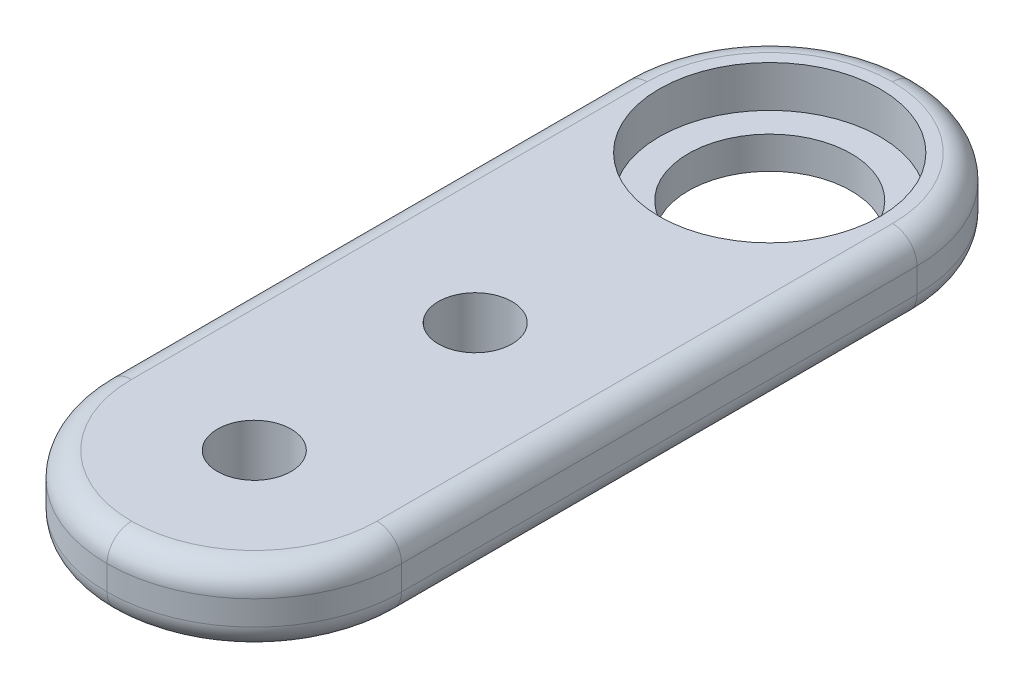
SolidWorks part; units mm, degrees
material "6061 Alloy"
ref_plane "Front Plane" through (0, 0, 0) normal (0, 0, 1) x (1, 0, 0)
ref_plane "Top Plane" through (0, 0, 0) normal (0, 1, 0) x (1, 0, 0)
ref_plane "Right Plane" through (0, 0, 0) normal (1, 0, 0) x (0, 0, -1)
sketch "Sketch1" plane through (0, 0, 0) normal (0, 1, 0) x (1, 0, 0)
  line L0 (0, 34.925) -> (0, -34.925) construction
  line L1 (-12.7, -34.925) -> (12.7, -34.925)
  line L2 (-12.7, -34.925) -> (-12.7, 34.925)
  line L3 (-12.7, 34.925) -> (12.7, 34.925)
  line L4 (12.7, -34.925) -> (12.7, 34.925)
  line L5 (-12.7, -34.925) -> (12.7, 34.925) construction
  line L6 (-12.7, 34.925) -> (12.7, -34.925) construction
  circle A1 centre (0, -3.175) radius 3.175
  circle A2 centre (0, -22.225) radius 3.175
  point P0 (0, 0)
  point P8 (0, 22.225)
  dimension "D3" = 25.4
  dimension "D2" = 12.7
  dimension "D6" = 6.35
  dimension "D1" = 25.4
  dimension "D4" = 19.05
  dimension "D5" = 12.7
extrude "Boss-Extrude1" add sketch "Sketch1" along normal blind 6.35
fillet "Fillet1" radius 12.7 4 edges at (-12.7, 3.175, -34.925) (12.7, 3.175, -34.925) (-12.7, 3.175, 34.925) (12.7, 3.175, 34.925)
fillet "Fillet2" radius 2.1167 12 edges at (8.9803, 0, 31.2053) (12.7, 0, 0) (8.9803, 0, -31.2053) (-8.9803, 0, -31.2053) (-12.7, 0, 0) (-8.9803, 6.35, -31.2053) (8.9803, 6.35, -31.2053) (12.7, 6.35, 0) (8.9803, 6.35, 31.2053) (-8.9803, 6.35, 31.2053) (-8.9803, 0, 31.2053) (-12.7, 6.35, 0)
ref_plane "Plane1" through (0, 0, 0) normal (-1, 0, 0) x (0, 0, 1)
sketch "Sketch3" plane through (0, 0, 0) normal (-1, 0, 0) x (0, 0, 1)
  line L0 (-22.225, 0) -> (-22.225, 6.35)
  line L1 (-31.75, 6.35) -> (-31.75, 2.7781)
  line L2 (-22.225, 6.35) -> (-32.8083, 6.35) construction
  line L3 (-31.75, 2.7781) -> (-22.225, 2.7781)
  line L5 (-29.2418, 2.7781) -> (-29.2418, 0)
  line L6 (34.925, 0) -> (-34.925, 0) construction
  line L7 (-29.2418, 0) -> (-22.225, 0) construction
  line L8 (-22.225, 6.35) -> (-31.75, 6.35) construction
  line L9 (-31.75, 6.35) -> (-31.75, 9.9219)
  line L10 (-31.75, 9.9219) -> (-22.225, 9.9219)
  line L11 (-22.225, 9.9219) -> (-22.225, 6.35)
  line L12 (-22.225, 9.9219) -> (-25.7593, -6.7056) construction
  line L13 (-20.5801, -5.4293) -> (-29.9715, -3.4331)
  line L14 (-29.9715, -3.4331) -> (-28.6513, 2.7781)
  line L15 (-22.225, 0) -> (-22.225, -5.0797)
  point P19 (-25.2758, -4.4312)
  dimension "D1" = 3.5719
  dimension "D2" = 12
  dimension "D3" = 9.6012
  dimension "D4" = 9.525
  dimension "D5" = 6.35
sketch "Sketch5" plane through (0, 6.35, 0) normal (0, 1, 0) x (1, 0, 0)
  circle A0 centre (0, 22.225) radius 9.525
  circle A1 centre (0, 22.225) radius 7.0168
extrude "Cut-Extrude2" cut sketch "Sketch5" against normal up to vertex (3.5719 mm away) up to point (0, 2.7781, -31.75)
extrude "Cut-Extrude3" cut sketch "Sketch5<2>" against normal up to vertex (6.35 mm away) contours A1 region at (0, 6.35, -22.225) up to point (0, 0, -29.2418)
sketch "Sketch5<2>" plane through (0, 6.35, 0) normal (0, 1, 0) x (1, 0, 0) same geometry as "Sketch5"
